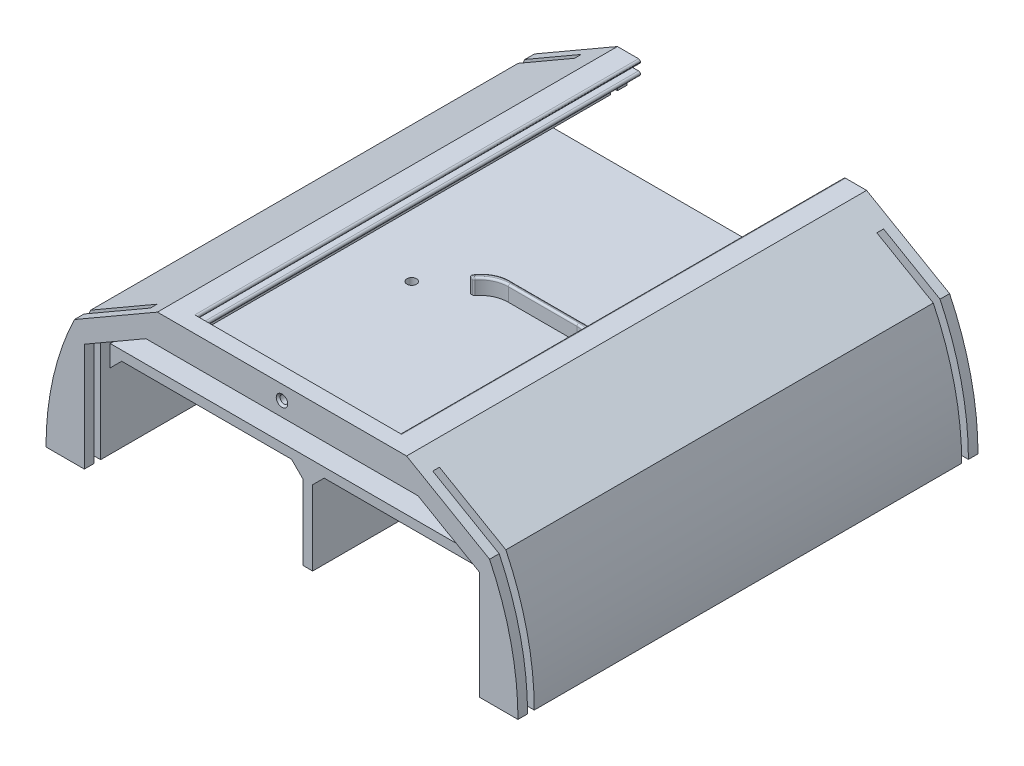
SolidWorks part; units mm, degrees
ref_plane "Front Plane" through (0, 0, 0) normal (0, 0, 1) x (1, 0, 0)
ref_plane "Top Plane" through (0, 0, 0) normal (0, 1, 0) x (1, 0, 0)
ref_plane "Right Plane" through (0, 0, 0) normal (1, 0, 0) x (0, 0, -1)
sketch "Sketch1" plane through (0, 0, 0) normal (0, 0, 1) x (1, 0, 0)
  line L0 (-65, 90) -> (-108.3013, 65)
  line L1 (-65, -90) -> (65, -90)
  line L3 (-65, 90) -> (65, 90)
  line L5 (-65, -90) -> (65, 90) construction
  line L6 (-65, 90) -> (65, -90) construction
  line L7 (-65, -90) -> (-108.3013, -65)
  line L8 (65, 90) -> (108.3013, 65)
  line L9 (65, -90) -> (108.3013, -65)
  arc A1 (-108.3013, 65) -> (-108.3013, -65) centre (26.8838, 0) ccw
  arc A4 (108.3013, 65) -> (108.3013, -65) centre (-26.8838, 0) cw
  point P0 (0, 0)
  point P7 (0, -90)
  dimension "D13" = 150
  dimension "D14" = 150
  dimension "D1" = 180
  dimension "D2" = 130
  dimension "D3" = 130
  dimension "D4" = 0
  dimension "D5" = 50
  dimension "D6" = 150
  dimension "D7" = 50
  dimension "D8" = 150
  dimension "D9" = 50
  dimension "D10" = 150
  dimension "D11" = 50
  dimension "D12" = 150
extrude "Boss-Extrude1" add sketch "Sketch1" along normal blind 240
sketch "Sketch2" plane through (0, 0, 240) normal (0, 0, 1) x (1, 0, 0)
  line L0 (-70.9808, 75) -> (70.9808, 75)
  line L1 (70.9808, 75) -> (103.1162, 56.4466)
  line L3 (65, 90) -> (-65, 90) construction
  line L4 (-70.9808, -75) -> (70.9808, -75)
  line L5 (70.9808, -75) -> (103.1162, -56.4466)
  line L6 (-65, -90) -> (65, -90) construction
  line L7 (108.3013, 65) -> (65, 90) construction
  line L8 (65, -90) -> (108.3013, -65) construction
  line L9 (-70.9808, 75) -> (-103.1162, 56.4466)
  line L10 (-70.9808, -75) -> (-103.1162, -56.4466)
  line L13 (-65, 90) -> (-108.3013, 65) construction
  line L15 (-108.3013, -65) -> (-65, -90) construction
  line L16 (-103.1162, 56.4466) -> (-103.1162, -56.4466)
  line L17 (103.1162, 56.4466) -> (103.1162, -56.4466)
  arc A0 (-108.3013, 65) -> (-108.3013, -65) centre (26.8838, 0) ccw construction
  arc A1 (108.3013, -65) -> (108.3013, 65) centre (-26.8838, 0) ccw construction
  point P24 (-123.1162, 0)
  point P28 (123.1162, 0)
  dimension "D1" = 15
  dimension "D2" = 10
  dimension "D3" = 20
  dimension "D4" = 15
  dimension "D5" = 20
  dimension "D7" = 10
  dimension "D8" = 10
  dimension "D10" = 10
sketch "Sketch3" plane through (0, 0, 0) normal (1, 0, 0) x (0, 0, -1)
  line L0 (-240, 90) -> (0, 90) construction
  line L1 (-235, 85) -> (-231.5, 85)
  line L2 (-235, 85) -> (-235, -85)
  line L3 (-235, -85) -> (-231.5, -85)
  line L4 (-231.5, 85) -> (-231.5, -85)
  line L5 (-240, -90) -> (0, -90) construction
  line L6 (-240, 65) -> (-240, -65) construction
  line L8 (-8.5, 82) -> (-5, 82)
  line L9 (-8.5, 82) -> (-8.5, -85)
  line L10 (-8.5, -85) -> (-5, -85)
  line L11 (-5, 82) -> (-5, -85)
  line L12 (0, -65) -> (0, 65) construction
  dimension "D1" = 5
  dimension "D2" = 5
  dimension "D3" = 5
  dimension "D4" = 3.5
  dimension "D5" = 8
  dimension "D6" = 5
  dimension "D7" = 5
  dimension "D8" = 3.5
extrude "Cut-Extrude4" cut sketch "Sketch2" against normal through all both and the other way through all
extrude "Cut-Extrude5" cut sketch "Sketch3" against normal through all both and the other way through all
sketch "Sketch7" plane through (0, 0, 0) normal (1, 0, 0) x (0, 0, -1)
  line L0 (-231.5, 65) -> (-231.5, -65) construction
  line L1 (-226.5, 45) -> (-13.5, 45)
  line L2 (-226.5, 45) -> (-226.5, 50)
  line L3 (-226.5, 50) -> (-13.5, 50)
  line L4 (-13.5, 45) -> (-13.5, 50)
  line L5 (-226.5, 45) -> (-13.5, 50) construction
  line L6 (-226.5, 50) -> (-13.5, 45) construction
  line L7 (-8.5, -65) -> (-8.5, 65) construction
  line L8 (-8.5, 75) -> (-231.5, 75) construction
  point P0 (-120, 47.5)
  dimension "D1" = 5
  dimension "D2" = 5
  dimension "D3" = 5
  dimension "D4" = 25
extrude "Boss-Extrude4" add sketch "Sketch7" along normal up to surface and the other way up to surface up to face at (103.1162, 0, 120) other way up to face at (-103.1162, 0, 120)
chamfer "Chamfer7" distance 6 angle 45 2 edges at (103.1162, 45, 120) (-103.1162, 45, 120)
sketch "Sketch8" plane through (0, -75, 0) normal (0, 1, 0) x (1, 0, 0)
  line L0 (-78.8564, -8.5) -> (-108.3013, -8.5) construction
  line L1 (-2.5, -226.5) -> (2.5, -226.5)
  line L2 (-2.5, -226.5) -> (-2.5, -13.5)
  line L3 (-2.5, -13.5) -> (2.5, -13.5)
  line L4 (2.5, -226.5) -> (2.5, -13.5)
  line L5 (-2.5, -226.5) -> (2.5, -13.5) construction
  line L6 (-2.5, -13.5) -> (2.5, -226.5) construction
  line L7 (-108.3013, -231.5) -> (-73.6603, -231.5) construction
  point P0 (0, -120)
  dimension "D1" = 5
  dimension "D2" = 5
  dimension "D3" = 5
extrude "Boss-Extrude5" add sketch "Sketch8" along normal up to surface (120 mm away) up to face at (0, 45, 120)
chamfer "Chamfer8" distance 6 angle 45 4 edges at (-2.5, 45, 120) (2.5, 45, 120) (2.5, -75, 120) (-2.5, -75, 120)
sketch "Sketch10" plane through (0, 0, 0) normal (1, 0, 0) x (0, 0, -1)
  line L0 (-240, -90) -> (0, -90) construction
  line L1 (-132.5, -75) -> (-107.5, -75)
  line L2 (-132.5, -75) -> (-132.5, -69)
  line L3 (-132.5, -69) -> (-107.5, -69)
  line L4 (-107.5, -75) -> (-107.5, -69)
  line L5 (-132.5, -75) -> (-107.5, -69) construction
  line L6 (-132.5, -69) -> (-107.5, -75) construction
  line L7 (-13.5, -75) -> (-226.5, -75) construction
  line L8 (-226.5, -69) -> (-13.5, -69) construction
  point P0 (-120, -72)
  point P7 (-120, -90)
  point P8 (-120, -75)
  dimension "D1" = 0
  dimension "D2" = 0
  dimension "D3" = 0
  dimension "D4" = 25
extrude "Cut-Extrude6" cut sketch "Sketch10" against normal blind 176 and the other way blind 23
sketch "Sketch12" plane through (0, 0, 0) normal (1, 0, 0) x (0, 0, -1)
  line L5 (-10, -64) -> (-230, -64)
  line L6 (-230, -64) -> (-230, -75)
  line L7 (-230, -75) -> (-132.5, -75)
  line L8 (-132.5, -75) -> (-132.5, -69)
  line L9 (-132.5, -69) -> (-107.5, -69)
  line L10 (-107.5, -69) -> (-107.5, -75)
  line L11 (-107.5, -75) -> (-10, -75)
  line L13 (-231.5, 56.4466) -> (-231.5, -56.4466) construction
  line L15 (-8.5, -75) -> (-107.5, -75) construction
  line L16 (-240, -90) -> (0, -90) construction
  line L17 (-10, -75) -> (-10, -64)
  line L18 (-8.5, -85) -> (-8.5, -65) construction
  point P16 (-120, -69)
  point P19 (-120, -90)
  dimension "D1" = 11
  dimension "D2" = 1.5
  dimension "D3" = 1.5
  dimension "D4" = 0
  dimension "D5" = 0
  dimension "D6" = 25
  dimension "D7" = 6
  dimension "D8" = 6
extrude "Boss-Extrude6" add sketch "Sketch12" against normal blind 90
fillet "Fillet1" radius 10 1 edges at (0, -69.5, 10)
fillet "Fillet2" radius 10 1 edges at (0, -69.5, 230)
sketch "Sketch13" plane through (0, 0, 0) normal (1, 0, 0) x (0, 0, -1)
  line L0 (-240, 90) -> (0, 90) construction
  line L1 (-8.5, 75) -> (-231.5, 75) construction
  circle A0 centre (-173.35, 62) radius 2.5
  circle A1 centre (-66.65, 62) radius 2.5
  circle A2 centre (-120, 62) radius 2.5
  point P6 (-120, 90)
  dimension "D1" = 53.35
  dimension "D5" = 5
  dimension "D6" = 5
  dimension "D7" = 5
  dimension "D2" = 53.35
  dimension "D3" = 13
  dimension "D4" = 13
extrude "Cut-Extrude7" cut sketch "Sketch13" against normal through all
sketch "Sketch14" plane through (0, 50, 0) normal (0, 1, 0) x (1, 0, 0)
  line L0 (103.1162, -226.5) -> (-103.1162, -226.5) construction
  line L1 (-2.5, -226.5) -> (-2.5, -13.5) construction
  circle A0 centre (-52.5, -119.8) radius 2.5
  dimension "D1" = 5
  dimension "D2" = 106.7
  dimension "D3" = 50
extrude "Cut-Extrude8" cut sketch "Sketch14" against normal blind 47
sketch "Sketch15" plane through (-103.1162, 0, 0) normal (1, 0, 0) x (0, 0, -1)
  line L0 (-231.5, 56.4466) -> (-231.5, -56.4466) construction
  line L1 (-8.5, -56.4466) -> (-8.5, 56.4466) construction
  line L2 (-13.5, 39) -> (-226.5, 39) construction
  circle A0 centre (-172.99, 24) radius 2.5
  circle A1 centre (-67.25, 24) radius 2.5
  dimension "D1" = 58.51
  dimension "D3" = 5
  dimension "D4" = 5
  dimension "D2" = 58.75
  dimension "D5" = 15
extrude "Cut-Extrude9" cut sketch "Sketch15" against normal blind 36
sketch "Sketch16" plane through (0, -75, 0) normal (0, 1, 0) x (1, 0, 0)
  line L0 (70.9808, -8.5) -> (70.9808, -231.5) construction
  line L1 (23.5, -170) -> (29.5, -170)
  line L2 (23.5, -170) -> (23.5, -70)
  line L3 (23.5, -70) -> (29.5, -70)
  line L4 (29.5, -170) -> (29.5, -70)
  line L5 (8.5, -13.5) -> (8.5, -107.5) construction
  line L7 (39.5, -162.5) -> (59.5, -162.5)
  line L8 (39.5, -162.5) -> (39.5, -77.5)
  line L9 (39.5, -77.5) -> (59.5, -77.5)
  line L10 (59.5, -162.5) -> (59.5, -77.5)
  point P4 (23.5, -120)
  point P7 (70.9808, -120)
  point P14 (59.5, -120)
  dimension "D1" = 6
  dimension "D2" = 100
  dimension "D3" = 0
  dimension "D4" = 15
  dimension "D5" = 20
  dimension "D6" = 85
  dimension "D7" = 0
  dimension "D8" = 10
extrude "Cut-Extrude10" cut sketch "Sketch16" against normal blind 8
sketch "Sketch20" plane through (0, -75, 0) normal (0, 1, 0) x (1, 0, 0)
  line L0 (59.5, -77.5) -> (39.5, -77.5) construction
  line L1 (23, -70) -> (21, -70)
  line L2 (23, -70) -> (23, -170)
  line L3 (23, -170) -> (21, -170)
  line L4 (21, -70) -> (21, -170)
  line L5 (30, -70) -> (32, -70)
  line L6 (30, -70) -> (30, -170)
  line L7 (30, -170) -> (32, -170)
  line L8 (32, -70) -> (32, -170)
  line L9 (37.5, -77.5) -> (39, -77.5)
  line L10 (37.5, -77.5) -> (37.5, -162.5)
  line L11 (37.5, -162.5) -> (39, -162.5)
  line L12 (39, -77.5) -> (39, -162.5)
  line L13 (61.5, -162.5) -> (60, -162.5)
  line L14 (61.5, -162.5) -> (61.5, -77.5)
  line L15 (61.5, -77.5) -> (60, -77.5)
  line L16 (60, -162.5) -> (60, -77.5)
  line L17 (39.5, -162.5) -> (59.5, -162.5) construction
  line L18 (29.5, -70) -> (23.5, -70) construction
  line L19 (23.5, -170) -> (29.5, -170) construction
  line L20 (29.5, -170) -> (29.5, -70) construction
  line L21 (23.5, -70) -> (23.5, -170) construction
  line L22 (39.5, -77.5) -> (39.5, -162.5) construction
  line L23 (59.5, -162.5) -> (59.5, -77.5) construction
  dimension "D1" = 1.5
  dimension "D2" = 1.5
  dimension "D3" = 2
  dimension "D4" = 2
  dimension "D5" = 0.5
  dimension "D6" = 0.5
  dimension "D7" = 0.5
  dimension "D8" = 0.5
extrude "Boss-Extrude7" add sketch "Sketch20" along normal blind 8
sketch "Sketch21" plane through (0, 0, 170) normal (0, 0, 1) x (1, 0, 0)
  line L0 (22.5, -67) -> (21, -73.7542)
  line L1 (21, -67) -> (21, -75) construction
  line L2 (21, -73.7542) -> (21, -67)
  line L3 (21, -67) -> (22.5, -67)
  line L4 (30.5, -67) -> (32, -67)
  line L5 (32, -67) -> (32, -73.7542)
  line L6 (32, -67) -> (32, -75) construction
  line L7 (32, -73.7542) -> (30.5, -67)
  line L8 (38.5, -67) -> (37.5, -73.7542)
  line L9 (37.5, -67) -> (37.5, -75) construction
  line L10 (37.5, -73.7542) -> (37.5, -67)
  line L11 (37.5, -67) -> (38.5, -67)
  line L12 (60.5, -67) -> (61.5, -73.7542)
  line L13 (61.5, -67) -> (61.5, -75) construction
  line L14 (61.5, -73.7542) -> (61.5, -67)
  line L15 (61.5, -67) -> (60.5, -67)
  line L16 (21, -67) -> (23, -67) construction
  line L17 (30, -67) -> (32, -67) construction
  line L18 (37.5, -67) -> (39, -67) construction
  line L19 (60, -67) -> (61.5, -67) construction
  dimension "D1" = 1.5
  dimension "D2" = 1.5
  dimension "D3" = 1
  dimension "D4" = 1
extrude "Cut-Extrude11" cut sketch "Sketch21" against normal up to next
fillet "Fillet4" radius 0.25 16 edges at (60.25, -67, 77.5) (38.75, -67, 77.5) (60.25, -67, 162.5) (38.75, -67, 162.5) (38.5, -67, 120) (39, -67, 120) (60, -67, 120) (60.5, -67, 120) (22.75, -67, 170) (22.5, -67, 120) (23, -67, 120) (22.75, -67, 70) (30.25, -67, 70) (30.25, -67, 170) (30.5, -67, 120) (30, -67, 120)
fillet "Fillet5" radius 1 4 edges at (26.5, -75, 170) (49.5, -75, 162.5) (26.5, -75, 70) (49.5, -75, 77.5)
sketch "Sketch22" plane through (61.5, 0, 0) normal (1, 0, 0) x (0, 0, -1)
  line L0 (-162.5, -75) -> (-77.5, -75) construction
  line L1 (-130, -75) -> (-110, -75)
  line L2 (-130, -75) -> (-130, -65)
  line L3 (-130, -65) -> (-110, -65)
  line L4 (-110, -75) -> (-110, -65)
  point P6 (-120, -75)
  point P7 (-120, -75)
  dimension "D1" = 20
  dimension "D2" = 10
extrude "Cut-Extrude12" cut sketch "Sketch22" against normal blind 43
chamfer "Chamfer9" distance 1 angle 45 16 edges at (60.75, -75, 77.5) (38.25, -75, 77.5) (31, -75, 70) (22, -75, 70) (22, -75, 110) (22, -75, 170) (31, -75, 170) (38.25, -75, 162.5) (60.75, -75, 162.5) (60.75, -75, 110) (31, -75, 110) (38.25, -75, 110) (22, -75, 130) (31, -75, 130) (38.25, -75, 130) (60.75, -75, 130)
sketch "Sketch24" plane through (0, 50, 0) normal (0, 1, 0) x (1, 0, 0)
  line L0 (-17.9178, -104) -> (17.9178, -104)
  line L1 (103.1162, -13.5) -> (103.1162, -226.5) construction
  line L5 (-32.9693, -110.0691) -> (-29.9693, -110.0691)
  line L6 (-17.9178, -101.5752) -> (17.9178, -101.5752)
  line L7 (29.9693, -110.0691) -> (32.9693, -110.0691)
  arc A0 (-17.9178, -104) -> (-29.9693, -110.0691) centre (-17.9178, -119) ccw
  arc A1 (17.9178, -104) -> (29.9693, -110.0691) centre (17.9178, -119) cw
  arc A3 (-32.9693, -110.0691) -> (-17.9178, -101.5752) centre (-19.4178, -116.5) cw
  arc A4 (32.9693, -110.0691) -> (17.9178, -101.5752) centre (19.4178, -116.5) ccw
  point P3 (0, -104)
  point P6 (103.1162, -120)
  dimension "D3" = 15
  dimension "D4" = 15
  dimension "D5" = 1.5
  dimension "D7" = 15
  dimension "D8" = 15
  dimension "D11" = 3
  dimension "D12" = 3
  dimension "D1" = 0
  dimension "D2" = 16
  dimension "D6" = 2.5
  dimension "D9" = 1.5
  dimension "D10" = 2.5
extrude "Boss-Extrude8" add sketch "Sketch24" along normal blind 8
fillet "Fillet6" radius 1 4 edges at (32.9693, 54, 110.0691) (29.9693, 54, 110.0691) (-32.9693, 54, 110.0691) (-29.9693, 54, 110.0691)
fillet "Fillet7" radius 1 12 edges at (-26.0172, 58, 103.0297) (-32.1578, 58, 109.5535) (-30.8728, 58, 110.0691) (-30.0273, 58, 109.9693) (-24.4502, 58, 105.4972) (26.0172, 58, 103.0297) (32.1578, 58, 109.5535) (30.8728, 58, 110.0691) (30.0273, 58, 109.9693) (24.4502, 58, 105.4972) (0, 58, 101.5752) (0, 58, 104)
sketch "Sketch25" plane through (0, -64, 0) normal (0, 1, 0) x (1, 0, 0)
  line L0 (-90, -10) -> (-7.5993, -10) construction
  line L1 (-2.5, -13.5) -> (-2.5, -226.5) construction
  line L3 (-90, -230) -> (-7.5993, -230) construction
  circle A0 centre (-48.7997, -46.5) radius 35
  circle A1 centre (-48.7997, -120) radius 35
  circle A2 centre (-48.7997, -193.5) radius 35
  point P9 (-48.7997, -10)
  point P13 (-2.5, -120)
  dimension "D1" = 70
  dimension "D2" = 70
  dimension "D3" = 70
  dimension "D4" = 36.5
  dimension "D5" = 36.5
extrude "Cut-Extrude13" cut sketch "Sketch25" against normal blind 5
sketch "Sketch26" plane through (0, 50, 0) normal (0, 1, 0) x (1, 0, 0)
  line L0 (70.9808, -8.5) -> (70.9808, -231.5) construction
  line L1 (73.9808, -155) -> (98.9808, -155)
  line L2 (73.9808, -155) -> (73.9808, -85)
  line L3 (73.9808, -85) -> (98.9808, -85)
  line L4 (98.9808, -155) -> (98.9808, -85)
  line L5 (73.9808, -155) -> (98.9808, -85) construction
  line L6 (73.9808, -85) -> (98.9808, -155) construction
  line L7 (108.3013, -231.5) -> (108.3013, -8.5) construction
  point P0 (86.4808, -120)
  point P9 (108.3013, -120)
  dimension "D1" = 70
  dimension "D2" = 25
  dimension "D3" = 3
  dimension "D4" = 0
extrude "Cut-Extrude14" cut sketch "Sketch26" against normal blind 12.5 from offset 105 offset against normal yes
sketch "Sketch27" plane through (0, -67.5, 0) normal (0, 1, 0) x (1, 0, 0)
  line L0 (83.9711, -155) -> (98.9808, -155) construction
  line L1 (83.9711, -85) -> (73.9711, -85)
  line L2 (83.9711, -85) -> (83.9711, -155)
  line L3 (83.9711, -155) -> (73.9711, -155)
  line L4 (73.9711, -85) -> (73.9711, -155)
  dimension "D1" = 10
extrude "Boss-Extrude9" add sketch "Sketch27" against normal blind 9
fillet "Fillet8" radius 1 5 edges at (78.9711, -67.5, 155) (73.9711, -70.3868, 155) (73.9711, -67.5, 120) (78.9711, -67.5, 85) (73.9711, -70.3868, 85)
sketch "Sketch28" plane through (0, 0, 155) normal (0, 0, 1) x (1, 0, 0)
  line L0 (73.9711, -73.2735) -> (83.9711, -67.5)
  line L2 (73.9711, -73.2735) -> (73.9711, -67.5)
  line L3 (73.9711, -67.5) -> (83.9711, -67.5)
extrude "Cut-Extrude15" cut sketch "Sketch28" against normal blind 10 from offset 30 offset against normal yes
fillet "Fillet9" radius 1 6 edges at (79.4711, -67.5, 125) (74.264, -67.7929, 125) (79.4711, -67.5, 115) (74.264, -67.7929, 115) (73.9711, -70.8868, 125) (73.9711, -70.8868, 115)
fillet "Fillet10" radius 2 3 edges at (91.476, -63.1671, 155) (98.9808, -58.8342, 120) (91.476, -63.1671, 85)
chamfer "Chamfer10" distance 1 angle 45 3 edges at (-48.7997, -64, 228.5) (-48.7997, -64, 81.5) (-48.7997, -64, 155)
sketch "Sketch29" plane through (0, 0, 0) normal (0, 0, 1) x (1, 0, 0)
  line L1 (-135.4816, 0) -> (144.3449, 0)
  line L2 (-135.4816, 0) -> (-135.4816, -99.522)
  line L3 (-135.4816, -99.522) -> (144.3449, -99.522)
  line L4 (144.3449, 0) -> (144.3449, -99.522)
extrude "Cut-Extrude16" cut sketch "Sketch29" against normal through all both and the other way through all
sketch "Sketch30" plane through (0, 0, 0) normal (0, -1, 0) x (1, 0, 0)
  line L0 (-123.1162, 231.5) -> (-103.1162, 231.5) construction
  line L1 (-118.1162, 191.5) -> (-108.1162, 191.5)
  line L2 (-118.1162, 191.5) -> (-118.1162, 48.5)
  line L3 (-118.1162, 48.5) -> (-108.1162, 48.5)
  line L4 (-108.1162, 191.5) -> (-108.1162, 48.5)
  line L5 (108.1162, 191.5) -> (118.1162, 191.5)
  line L6 (108.1162, 191.5) -> (108.1162, 48.5)
  line L7 (108.1162, 48.5) -> (118.1162, 48.5)
  line L8 (118.1162, 191.5) -> (118.1162, 48.5)
  line L9 (-103.1162, 8.5) -> (-123.1162, 8.5) construction
  line L10 (103.1162, 231.5) -> (123.1162, 231.5) construction
  line L11 (123.1162, 8.5) -> (103.1162, 8.5) construction
  line L12 (-123.1162, 8.5) -> (-123.1162, 231.5) construction
  line L13 (-103.1162, 231.5) -> (-103.1162, 8.5) construction
  line L14 (103.1162, 226.5) -> (103.1162, 13.5) construction
  line L15 (123.1162, 231.5) -> (123.1162, 8.5) construction
  dimension "D1" = 40
  dimension "D2" = 40
  dimension "D3" = 40
  dimension "D4" = 40
  dimension "D5" = 5
  dimension "D6" = 5
  dimension "D7" = 5
  dimension "D8" = 5
extrude "Cut-Extrude17" cut sketch "Sketch30" against normal blind 20
chamfer "Chamfer11" distance 3 angle 45 8 edges at (113.1162, 0, 48.5) (108.1162, 0, 120) (118.1162, 0, 120) (113.1162, 0, 191.5) (-113.1162, 0, 191.5) (-108.1162, 0, 120) (-113.1162, 0, 48.5) (-118.1162, 0, 120)
sketch "Sketch32" plane through (0, 0, 240) normal (0, 0, 1) x (1, 0, 0)
  line L0 (-53, 90) -> (-53, 88)
  line L1 (65, 90) -> (-65, 90) construction
  line L2 (-53, 88) -> (-60, 88)
  line L3 (-60, 88) -> (-60, 84.5)
  line L4 (-60, 84.5) -> (-53, 84.5)
  line L5 (-53, 84.5) -> (-53, 82.5)
  line L6 (-53, 82.5) -> (-60, 82.5)
  line L7 (-60, 82.5) -> (-60, 75)
  line L8 (-70.9808, 75) -> (70.9808, 75) construction
  line L9 (-60, 75) -> (60, 75)
  line L10 (60, 75) -> (60, 82.5)
  line L11 (60, 82.5) -> (53, 82.5)
  line L12 (53, 82.5) -> (53, 84.5)
  line L13 (53, 84.5) -> (60, 84.5)
  line L14 (60, 84.5) -> (60, 88)
  line L15 (60, 88) -> (53, 88)
  line L16 (53, 88) -> (53, 90)
  line L17 (53, 90) -> (-53, 90)
  dimension "D1" = 12
  dimension "D2" = 5
  dimension "D3" = 7
  dimension "D4" = 5
  dimension "D5" = 2
  dimension "D6" = 2
  dimension "D7" = 3.5
  dimension "D8" = 2
  dimension "D9" = 2
  dimension "D10" = 3.5
extrude "Cut-Extrude19" cut sketch "Sketch32" against normal through all from offset 8.5 offset against normal yes
fillet "Fillet11" radius 1 8 edges at (-53, 90, 115.75) (-53, 88, 115.75) (-53, 84.5, 115.75) (-53, 82.5, 115.75) (53, 90, 115.75) (53, 88, 115.75) (53, 84.5, 115.75) (53, 82.5, 115.75)
sketch "Sketch33" plane through (0, 0, 240) normal (0, 0, 1) x (1, 0, 0)
  line L1 (65, 90) -> (-65, 90) construction
  circle A0 centre (0, 82.5) radius 2
  dimension "D1" = 7.5
  dimension "D2" = 4
extrude "Cut-Extrude20" cut sketch "Sketch33" against normal blind 4.5
chamfer "Chamfer12" distance 1 angle 45 1 edges at (2, 82.5, 240)
equation "\"`\"=64"
